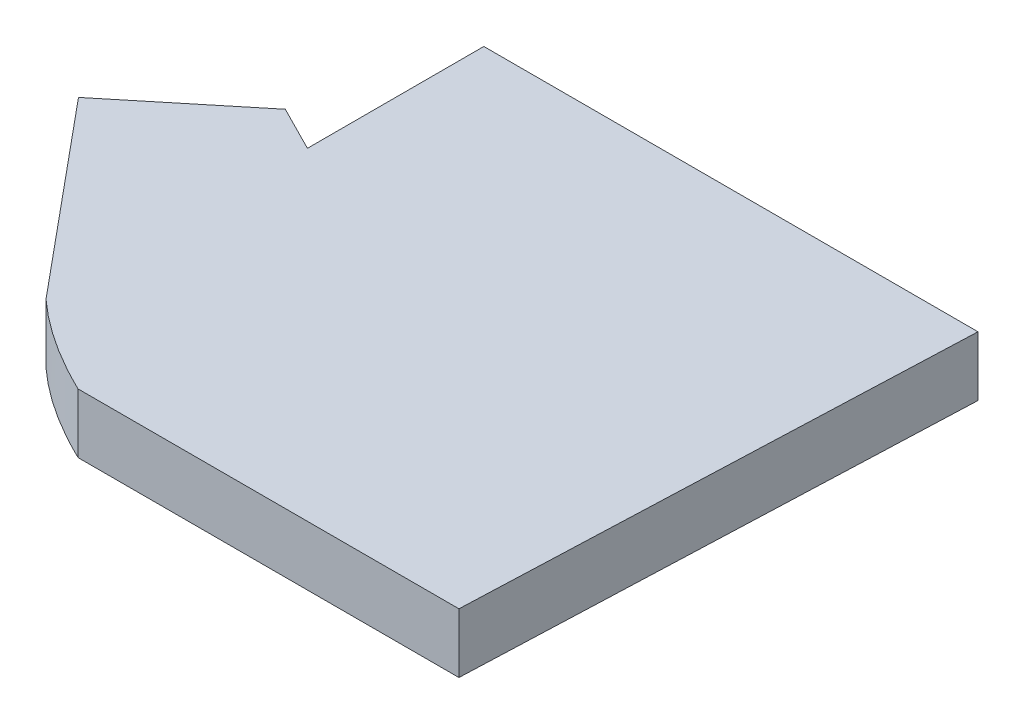
SolidWorks part; units mm, degrees
ref_plane "Front Plane" through (0, 0, 0) normal (0, 0, 1) x (1, 0, 0)
ref_plane "Top Plane" through (0, 0, 0) normal (0, 1, 0) x (1, 0, 0)
ref_plane "Right Plane" through (0, 0, 0) normal (1, 0, 0) x (0, 0, -1)
sketch "Sketch1" plane through (0, 0, 0) normal (0, 1, 0) x (1, 0, 0)
  line L0 (-13.9285, -6.6) -> (69.0715, -6.6)
  line L1 (69.0715, -6.6) -> (65.7758, -90.4854)
  line L3 (65.7758, -90.4854) -> (1.8057, -90.4854)
  line L4 (-13.9285, -6.6) -> (-13.9285, -36.2299)
  line L5 (-40.5595, -48.0529) -> (-13.9285, -80.1379)
  line L6 (-21.4687, -32.4055) -> (-40.5595, -48.0529)
  line L7 (-13.9285, -36.2299) -> (-21.4687, -32.4055)
  line L8 (-38.2991, -55.5466) -> (-20.5101, -40.9662) construction
  line L12 (4.1, -4.6) -> (-4.1, -4.6) construction
  spline S1 degree 2 poles (-13.9285, -80.1379) (-7.5226, -85.9916) (1.8057, -90.4854) knots 0 0 0 1 1 1
  point P1 (-13.9285, 6.9295)
  point P7 (-13.9285, -36.2299)
  dimension "D1" = 83
  dimension "D2" = 2
extrude "Boss-Extrude1" add sketch "Sketch1" along normal blind 5 and the other way blind 5
